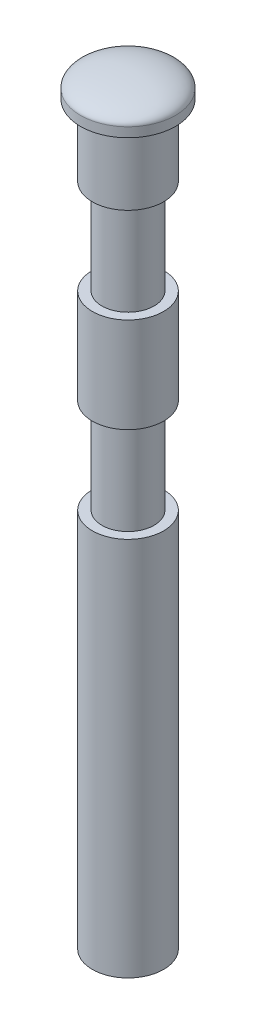
SolidWorks part; units mm, degrees
ref_plane "前视基准面" through (0, 0, 0) normal (0, 0, 1) x (1, 0, 0)
ref_plane "上视基准面" through (0, 0, 0) normal (0, 1, 0) x (1, 0, 0)
ref_plane "右视基准面" through (0, 0, 0) normal (1, 0, 0) x (0, 0, -1)
sketch "草图1" plane through (0, 0, 0) normal (0, 0, 1) x (1, 0, 0)
  line L0 (0, 0) -> (2, 0)
  line L1 (2, 0) -> (2, 15.7)
  line L2 (0, 0) -> (0, 15.7)
  line L3 (1, 22.0107) -> (1, -5.9022) construction
  ellipse E0 centre (1, 15.7) end of major axis (2, 15.7) minor radius 0.3
  dimension "D1" = 0.3
  dimension "D2" = 2
  dimension "D3" = 15.7
  dimension "D4" = 0.3
revolve "旋转1" add sketch "草图1" angle 360 about L3 region at (1.5012, 7.7323, 0) region at (1.4244, 15.7, 0)
sketch "草图2" plane through (0, 0, 0) normal (0, -1, 0) x (1, 0, 0)
  circle A0 centre (1, 0) radius 1.2882
  circle A1 centre (1, 0) radius 0.75
  dimension "D1" = 1.5
extrude "切除-拉伸1" cut sketch "草图2" against normal blind 15.5
sketch "草图3" plane through (0, 0, 0) normal (0, -1, 0) x (-1, 0, 0)
  circle A0 centre (-1, 0) radius 0.3
  dimension "D1" = 0.6
extrude "切除-拉伸2" cut sketch "草图3" against normal blind 4
ref_plane "基准面1" through (0, 6, 0) normal (0, -1, 0) x (-1, 0, 0)
sketch "草图4" plane through (0, 6, 0) normal (0, -1, 0) x (-1, 0, 0)
  circle A0 centre (-1, 0) radius 0.75
curve "螺旋线/涡状线1" [suppressed] pitch 9 height 9 turns 1
sketch "草图5" [suppressed] plane through (0, 0, 0) normal (0, 0, 1) x (1, 0, 0)
  line L0 (1.75, 0) -> (1.75, 15.5) construction
  line L1 (1.775, 5.9567) -> (1.7, 6)
  line L2 (1.7, 6) -> (1.775, 6.0433)
  line L3 (1.775, 6.0433) -> (1.775, 5.9567)
  circle A0 centre (1.75, 6) radius 0.025 construction
  spline S0 degree 3 poles (1.75, 6) (1.75, 6.1872) (1.7109, 6.5626) (1.5441, 7.125) (1.2945, 7.6875) (1, 8.25) (0.7055, 8.8125) (0.4559, 9.375) (0.2891, 9.9375) (0.2305, 10.5) (0.2891, 11.0625) (0.4559, 11.625) (0.7055, 12.1875) (1, 12.75) (1.2945, 13.3125) (1.5441, 13.875) (1.7109, 14.4374) (1.75, 14.8128) (1.75, 15) knots 0 0 0 0 0.0625 0.125 0.1875 0.25 0.3125 0.375 0.4375 0.5 0.5625 0.625 0.6875 0.75 0.8125 0.875 0.9375 1 1 1 1 construction
  dimension "D1" = 0.05
sweep "切除-扫描1" [suppressed] cut profiles "草图5" path "螺旋线/涡状线1"
pattern_circular "阵列(圆周)10" [suppressed] count 30 over 360 reverse direction yes of bodies 109
sketch "草图6" plane through (0, 6, 0) normal (0, -1, 0) x (-1, 0, 0)
  circle A0 centre (-1, 0) radius 0.75
curve "螺旋线/涡状线2" [suppressed] pitch 9 height 9 turns 1
sketch "草图7" [suppressed] plane through (0, 0, 0) normal (0, 0, 1) x (1, 0, 0)
  line L0 (1.75, 6.0289) -> (1.75, 5.9711) construction
  line L1 (1.7, 6) -> (1.775, 5.9567)
  line L2 (1.775, 5.9567) -> (1.775, 6.0433)
  line L3 (1.775, 6.0433) -> (1.7, 6)
  circle A0 centre (1.75, 6) radius 0.025 construction
  dimension "D1" = 0.05
sweep "切除-扫描2" [suppressed] cut profiles "草图7" path "螺旋线/涡状线2"
pattern_circular "阵列(圆周)12" [suppressed] count 20 over 360 of bodies 112
sketch "草图8" plane through (0, 0, 0) normal (0, 0, 1) x (1, 0, 0)
  line L0 (1, 0) -> (1, 21.5854) construction
  line L1 (0.25, 0) -> (1.75, 0) construction
  line L3 (1.9435, 14) -> (1.55, 14)
  line L4 (1.9435, 14) -> (1.9435, 12)
  line L5 (1.9435, 12) -> (1.55, 12)
  line L6 (1.55, 14) -> (1.55, 12)
  line L7 (1.9435, 10) -> (1.55, 10)
  line L8 (1.9435, 10) -> (1.9435, 8)
  line L9 (1.9435, 8) -> (1.55, 8)
  line L10 (1.55, 10) -> (1.55, 8)
  dimension "D1" = 2
  dimension "D2" = 2
  dimension "D3" = 0.55
  dimension "D4" = 0.55
  dimension "D5" = 2
  dimension "D6" = 8
revolve "切除-旋转1" cut sketch "草图8" angle 360 about L0
